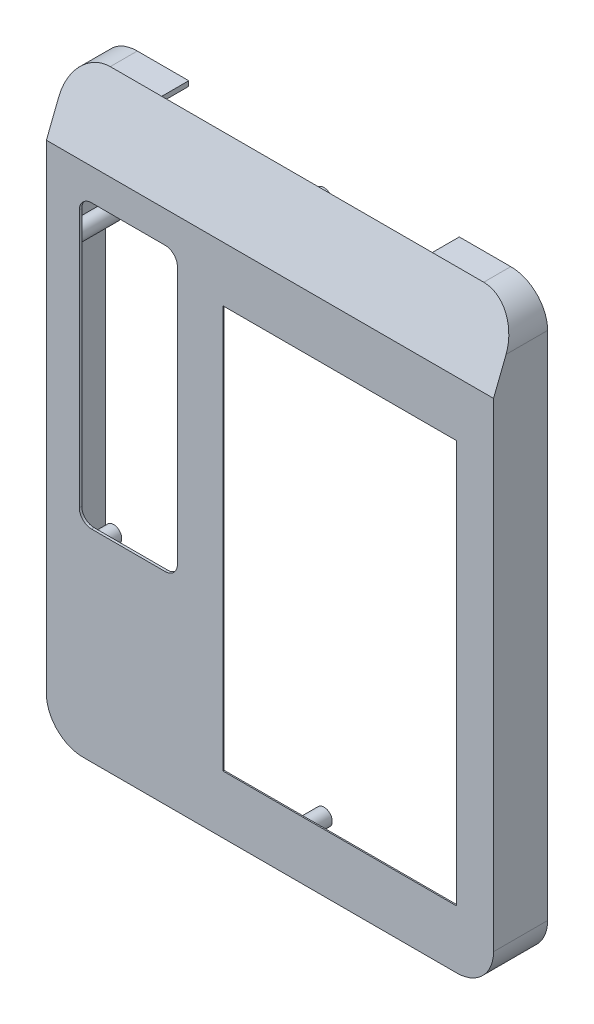
SolidWorks part; units mm, degrees
ref_plane "Front Plane" through (0, 0, 0) normal (0, 0, 1) x (1, 0, 0)
ref_plane "Top Plane" through (0, 0, 0) normal (0, 1, 0) x (1, 0, 0)
ref_plane "Right Plane" through (0, 0, 0) normal (1, 0, 0) x (0, 0, -1)
sketch "Sketch1" plane through (0, 0, 0) normal (0, 0, 1) x (1, 0, 0)
  line L1 (-76, 119) -> (76, 119)
  line L2 (-91, 104) -> (-91, -104)
  line L3 (-76, -119) -> (76, -119)
  line L4 (91, 104) -> (91, -104)
  line L5 (-91, 119) -> (91, -119) construction
  line L6 (-91, -119) -> (91, 119) construction
  arc A0 (76, -119) -> (91, -104) centre (76, -104) ccw
  arc A1 (-76, -119) -> (-91, -104) centre (-76, -104) cw
  arc A2 (91, 104) -> (76, 119) centre (76, 104) ccw
  arc A3 (-76, 119) -> (-91, 104) centre (-76, 104) ccw
  point P0 (0, 0)
  dimension "D3" = 15
  dimension "D4" = 15
  dimension "D1" = 182
  dimension "D2" = 238
extrude "Boss-Extrude1" add sketch "Sketch1" along normal blind 22
sketch "Sketch3" plane through (-91, 0, 0) normal (-1, 0, 0) x (0, 0, 1)
  line L0 (11, 119) -> (22, 91.0533)
  line L1 (22, 119) -> (0, 119) construction
  line L2 (22, 104) -> (22, -104) construction
  line L3 (11, 119) -> (22, 119)
  line L4 (22, 119) -> (22, 91.0533)
extrude "Cut-Extrude2" cut sketch "Sketch3" against normal mid plane 381
shell "Shell2" thickness 2 removed face at (0, 0, 0)
sketch "Sketch5" plane through (0, 0, 20) normal (0, 0, -1) x (-1, 0, 0)
  line L0 (0, -117) -> (0, -108.75) construction
  line L1 (76, -117) -> (-76, -117) construction
  line L2 (-85.1924, -113.1924) -> (-79.3588, -107.3588) construction
  line L3 (85.1924, -113.1924) -> (79.3588, -107.3588) construction
  line L4 (0, -117) -> (0, 119) construction
  line L5 (-76, 119) -> (76, 119) construction
  line L6 (0, 1) -> (89, 1) construction
  line L7 (89, 90.6738) -> (89, -104) construction
  line L9 (44.5, 1) -> (44.5, -1.75) construction
  line L10 (0, -1.75) -> (87.5, -1.75) construction
  arc A1 (-89, -104) -> (-76, -117) centre (-76, -104) ccw construction
  arc A3 (76, -117) -> (89, -104) centre (76, -104) ccw construction
  circle A11 centre (0, -112.875) radius 3.35
  circle A12 centre (-82.2756, -110.2756) radius 3.35
  circle A13 centre (82.2756, -110.2756) radius 3.35
extrude "Boss-Extrude7" add sketch "Sketch5" along normal up to surface (20 mm away) up to face at (0, 0, 0)
sketch "Sketch6" plane through (0, 0, 0) normal (0, 0, -1) x (-1, 0, 0)
  line L0 (0, 119) -> (0, 105.5) construction
  line L2 (-76, 119) -> (76, 119) construction
  line L3 (86.6066, 114.6066) -> (77.0607, 105.0607) construction
  line L4 (-86.6066, 114.6066) -> (-77.0607, 105.0607) construction
  circle A0 centre (0, 105.5) radius 3.375
  arc A1 (91, 104) -> (76, 119) centre (76, 104) ccw construction
  arc A2 (-76, 119) -> (-91, 104) centre (-76, 104) ccw construction
  circle A3 centre (-81.8336, 109.8336) radius 3.3
  circle A4 centre (81.8336, 109.8336) radius 3.3
extrude "Boss-Extrude8" add sketch "Sketch6" against normal up to surface (14.1643 mm away) up to face at (0, 104.7887, 14.4443)
sketch "Sketch7" plane through (0, 0, 0) normal (0, 0, -1) x (-1, 0, 0)
  circle A0 centre (-82.2756, -110.2756) radius 2
  circle A1 centre (0, -112.875) radius 2
  circle A2 centre (82.2756, -110.2756) radius 2
  circle A3 centre (81.8336, 109.8336) radius 2
  circle A4 centre (0, 105.5) radius 2
  circle A5 centre (-81.8336, 109.8336) radius 2
extrude "Cut-Extrude3" cut sketch "Sketch7" against normal blind 4
sketch "Sketch8" plane through (0, 119, 0) normal (0, 1, 0) x (1, 0, 0)
  line L0 (0, 0) -> (0, -11) construction
  line L1 (76, -11) -> (-76, -11) construction
  line L3 (-55.0651, 0) -> (55.0651, 0)
  line L4 (-55.0651, 0) -> (-55.0651, -11)
  line L5 (-55.0651, -11) -> (55.0651, -11)
  line L6 (55.0651, 0) -> (55.0651, -11)
  line L7 (-55.0651, 0) -> (55.0651, -11) construction
  line L8 (-55.0651, -11) -> (55.0651, 0) construction
  point P5 (0, -5.5)
extrude "Cut-Extrude4" cut sketch "Sketch8" against normal blind 10
sketch "Sketch9" plane through (0, 0, 0) normal (0, 0, -1) x (-1, 0, 0)
  line L0 (-65.5326, 119) -> (-111.4143, 120.4528) construction
  line L1 (-76, 119) -> (-55.0651, 119) construction
  line L2 (-111.4143, 120.4528) -> (-111.4143, 57.9528) construction
  line L3 (-111.4143, 57.9528) -> (-84.0659, 57.9528) construction
  line L4 (-89, 57.9528) -> (-82.35, 57.9528) construction
  line L5 (-89, -104) -> (-89, 90.6738) construction
  line L6 (0, 0) -> (0, 151.1593) construction
  line L7 (-85.675, 57.9528) -> (-85.675, -56.0472) construction
  line L8 (-85.675, 0.9528) -> (89, 0.9528) construction
  line L9 (89, 90.6738) -> (89, -104) construction
  circle A0 centre (-85.675, 57.9528) radius 3.325
  circle A1 centre (85.675, 57.9528) radius 3.325
  circle A2 centre (-85.675, -56.0472) radius 3.325
  circle A3 centre (85.675, -56.0472) radius 3.325
extrude "Boss-Extrude10" add sketch "Sketch9" against normal up to surface (20 mm away) separate body up to face at (-78.9256, -110.2756, 20)
sketch "Sketch10" plane through (0, 0, 0) normal (0, 0, -1) x (-1, 0, 0)
  circle A0 centre (-85.675, 57.9528) radius 2
  circle A1 centre (-85.675, -56.0472) radius 2
  circle A2 centre (85.675, -56.0472) radius 2
  circle A3 centre (85.675, 57.9528) radius 2
extrude "Cut-Extrude5" cut sketch "Sketch10" against normal blind 6
sketch "Sketch11" plane through (0, 0, 20) normal (0, 0, -1) x (-1, 0, 0)
  line L0 (-80, -117) -> (-80, -100.5) construction
  line L1 (76, -117) -> (-76, -117) construction
  line L2 (-80, -100.5) -> (-89, -100.5) construction
  line L3 (-89, -104) -> (-89, 104) construction
sketch "Sketch12" plane through (0, 0, 20) normal (0, 0, -1) x (-1, 0, 0)
  line L0 (19.1213, -95.3787) -> (-75.8787, -95.3787) construction
  line L1 (-77.8787, 76.6213) -> (24.1213, 76.6213)
  line L2 (-80.8787, 73.6213) -> (-80.8787, -98.3787)
  line L3 (-77.8787, -101.3787) -> (24.1213, -101.3787)
  line L4 (27.1213, 73.6213) -> (27.1213, -98.3787)
  line L5 (-80.8787, 76.6213) -> (27.1213, -101.3787) construction
  line L6 (-80.8787, -101.3787) -> (27.1213, 76.6213) construction
  line L7 (-75.8787, 68.6213) -> (19.1213, 68.6213)
  line L8 (-75.8787, 68.6213) -> (-75.8787, -95.3787)
  line L9 (-75.8787, -95.3787) -> (19.1213, -95.3787)
  line L10 (19.1213, 68.6213) -> (19.1213, -95.3787)
  line L11 (19.1213, 68.6213) -> (19.1213, -95.3787) construction
  arc A0 (24.1213, -101.3787) -> (27.1213, -98.3787) centre (24.1213, -98.3787) ccw
  arc A1 (-77.8787, -101.3787) -> (-80.8787, -98.3787) centre (-77.8787, -98.3787) cw
  arc A2 (-80.8787, 73.6213) -> (-77.8787, 76.6213) centre (-77.8787, 73.6213) cw
  arc A3 (27.1213, 73.6213) -> (24.1213, 76.6213) centre (24.1213, 73.6213) ccw
  point P0 (-26.8787, -12.3787)
  dimension "D1" = 3
extrude "Cut-Extrude6" cut sketch "Sketch12" against normal blind 10 contours L8 L7 L10 L9
extrude "Cut-Extrude7" cut sketch "Sketch12<3>" against normal blind 1.5
sketch "Sketch12<3>" plane through (0, 0, 20) normal (0, 0, -1) x (-1, 0, 0) same geometry as "Sketch12"
sketch "Sketch13" plane through (0, 0, 20) normal (0, 0, -1) x (-1, 0, 0)
  line L0 (57.6469, -36.814) -> (57.6469, 78.186) construction
  line L3 (72.6469, -36.814) -> (42.6469, -36.814) construction
  line L8 (42.6469, 78.186) -> (72.6469, 78.186) construction
  line L10 (41.7605, 83.4082) -> (73.5333, 83.4082)
  line L11 (31.7605, 73.4082) -> (31.7605, -32.0363)
  line L12 (41.7605, -42.0363) -> (73.5333, -42.0363)
  line L13 (83.5333, 73.4082) -> (83.5333, -32.0363)
  line L14 (31.7605, 83.4082) -> (83.5333, -42.0363) construction
  line L15 (31.7605, -42.0363) -> (83.5333, 83.4082) construction
  line L16 (42.6811, 78.186) -> (72.6128, 78.186)
  line L17 (37.6811, 73.186) -> (37.6811, -31.814)
  line L18 (42.6811, -36.814) -> (72.6128, -36.814)
  line L19 (77.6128, 73.186) -> (77.6128, -31.814)
  line L20 (37.6811, 78.186) -> (77.6128, -36.814) construction
  line L21 (37.6811, -36.814) -> (77.6128, 78.186) construction
  arc A0 (83.5333, -32.0363) -> (73.5333, -42.0363) centre (73.5333, -32.0363) cw
  arc A1 (41.7605, -42.0363) -> (31.7605, -32.0363) centre (41.7605, -32.0363) cw
  arc A2 (83.5333, 73.4082) -> (73.5333, 83.4082) centre (73.5333, 73.4082) ccw
  arc A3 (31.7605, 73.4082) -> (41.7605, 83.4082) centre (41.7605, 73.4082) cw
  arc A4 (77.6128, 73.186) -> (72.6128, 78.186) centre (72.6128, 73.186) ccw
  arc A5 (37.6811, 73.186) -> (42.6811, 78.186) centre (42.6811, 73.186) cw
  arc A6 (72.6128, -36.814) -> (77.6128, -31.814) centre (72.6128, -31.814) ccw
  arc A7 (42.6811, -36.814) -> (37.6811, -31.814) centre (42.6811, -31.814) cw
  point P6 (57.6469, 20.686)
  point P25 (57.6469, 20.686)
  dimension "D1" = 10
  dimension "D2" = 5
extrude "Cut-Extrude8" cut sketch "Sketch13" against normal blind 10 contours L17 A7 L18 A6 L19 A4 L16 A5
extrude "Cut-Extrude10" cut sketch "Sketch13<4>" against normal blind 1
sketch "Sketch13<4>" plane through (0, 0, 20) normal (0, 0, -1) x (-1, 0, 0) same geometry as "Sketch13"
sketch "Sketch14" plane through (0, 0, 20) normal (0, 0, -1) x (-1, 0, 0)
  line L0 (85.675, 57.9528) -> (85.1435, 57.9528) construction
  circle A0 centre (85.0219, -3.314) radius 0.9
  circle A1 centre (85.0219, 44.686) radius 0.9
  circle A2 centre (30.2719, 44.686) radius 0.9
  circle A3 centre (57.6469, 85.061) radius 0.9
  circle A4 centre (30.2719, -3.314) radius 0.9
  circle A5 centre (57.6469, -43.689) radius 0.9
extrude "Boss-Extrude11" add sketch "Sketch14" along normal blind 4
sketch "Sketch15" plane through (0, 0, 20) normal (0, 0, -1) x (-1, 0, 0)
  circle A0 centre (35.0406, -94.2777) radius 0.9
  circle A1 centre (35.0406, -48.5343) radius 0.9
  circle A2 centre (6.6656, 79.0773) radius 0.9
  circle A3 centre (-58.5844, 79.0773) radius 0.9
  circle A4 centre (-81.9594, 70.2023) radius 0.9
  circle A5 centre (-81.9594, -94.2777) radius 0.9
extrude "Boss-Extrude12" add sketch "Sketch15" along normal blind 10
